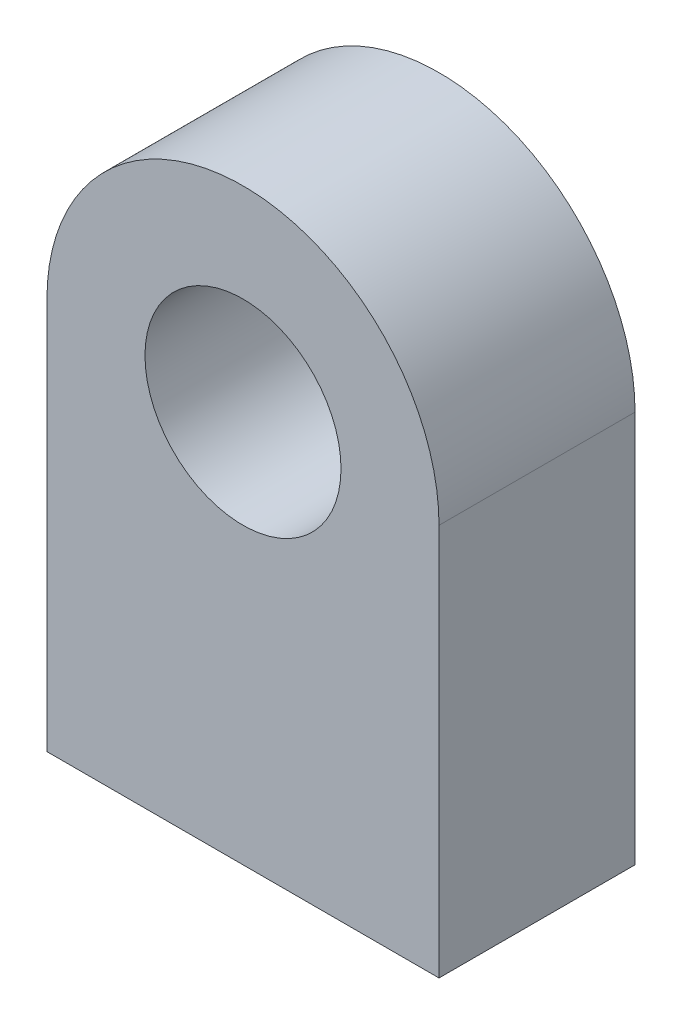
SolidWorks part; units mm, degrees
material "1060 Alloy"
ref_plane "Front Plane" through (0, 0, 0) normal (0, 0, 1) x (1, 0, 0)
ref_plane "Top Plane" through (0, 0, 0) normal (0, 1, 0) x (1, 0, 0)
ref_plane "Right Plane" through (0, 0, 0) normal (1, 0, 0) x (0, 0, -1)
sketch "Sketch1" plane through (0, 0, 0) normal (0, 0, 1) x (1, 0, 0)
  line L0 (0, 19.8538) -> (0, -21.8392) construction
  line L1 (-24.6755, 0) -> (26.59, 0) construction
  line L4 (-6.35, 0) -> (-6.35, -12.7)
  line L5 (-6.35, -12.7) -> (6.35, -12.7)
  line L6 (6.35, 0) -> (6.35, -12.7)
  line L7 (-2.8398, 5.6796) -> (6.35, -12.7) construction
  line L8 (-6.35, -12.7) -> (2.8398, 5.6796) construction
  circle A0 centre (0, 0) radius 3.175
  arc A1 (6.35, 0) -> (-6.35, 0) centre (0, 0) ccw
  point P12 (-6.35, 0)
  point P13 (0, 0)
  dimension "D1" = 6.35
  dimension "D2" = 12.7
  dimension "D3" = 12.7
extrude "Boss-Extrude1" add sketch "Sketch1" along normal blind 6.35
sketch "Sketch2" plane through (0, 0, 6.35) normal (0, 0, 1) x (1, 0, 0)
  line L0 (0, 12.118) -> (0, -18.5266) construction
